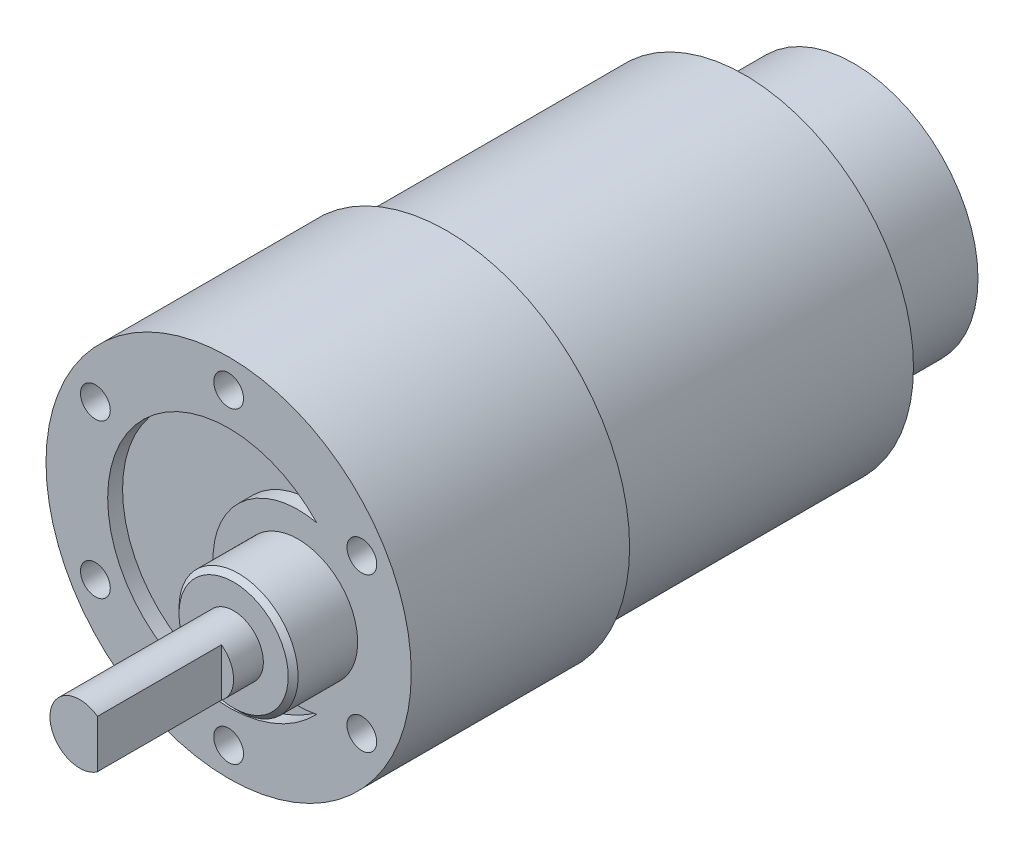
SolidWorks part; units mm, degrees
ref_plane "Front Plane" through (0, 0, 0) normal (0, 0, 1) x (1, 0, 0)
ref_plane "Top Plane" through (0, 0, 0) normal (0, 1, 0) x (1, 0, 0)
ref_plane "Right Plane" through (0, 0, 0) normal (1, 0, 0) x (0, 0, -1)
sketch "Sketch1" plane through (0, 0, 0) normal (0, 0, 1) x (1, 0, 0)
  circle A0 centre (0, 0) radius 17
  dimension "D1" = 34
extrude "Boss-Extrude1" add sketch "Sketch1" along normal blind 30
fillet "Fillet1" radius 1 1 edges at (17, 0, 30)
sketch "Sketch2" plane through (0, 0, 30) normal (0, 0, 1) x (1, 0, 0)
  circle A0 centre (0, 0) radius 18.4
extrude "Boss-Extrude2" add sketch "Sketch2" along normal blind 22
sketch "Sketch3" plane through (0, 0, 52) normal (0, 0, 1) x (1, 0, 0)
  circle A0 centre (0, 15.5) radius 1.5
  circle A1 centre (0, 0) radius 18.4 construction
  circle A2 centre (13.4234, 7.75) radius 1.5
  circle A3 centre (13.4234, -7.75) radius 1.5
  circle A4 centre (0, -15.5) radius 1.5
  circle A5 centre (-13.4234, -7.75) radius 1.5
  circle A6 centre (-13.4234, 7.75) radius 1.5
  dimension "D1" = 15.5
  dimension "D2" = 6
extrude "Cut-Extrude1" cut sketch "Sketch3" against normal blind 3
sketch "Sketch4" plane through (0, 0, 52) normal (0, 0, 1) x (1, 0, 0)
  circle A0 centre (7, 0) radius 6
  circle A1 centre (0, 15.5) radius 1.5 construction
  dimension "D1" = 12
  dimension "D2" = 7
extrude "Boss-Extrude3" add sketch "Sketch4" along normal blind 6.5
chamfer "Chamfer1" distance 0.5 angle 45 1 edges at (13, 0, 58.5)
sketch "Sketch5" plane through (0, 0, 58.5) normal (0, 0, 1) x (1, 0, 0)
  circle A0 centre (7, 0) radius 3
extrude "Boss-Extrude4" add sketch "Sketch5" along normal blind 15.5
sketch "Sketch6" plane through (0, 0, 52) normal (0, 0, 1) x (1, 0, 0)
  circle A0 centre (7, 0) radius 8.5659
  circle A1 centre (0, 0) radius 12.1872
extrude "Cut-Extrude3" cut sketch "Sketch6" against normal blind 1.5 contours A0 A1 region at (-3.6559, 0, 52)
sketch "Sketch7" plane through (0, 0, 0) normal (0, 0, -1) x (-1, 0, 0)
  circle A0 centre (0, 0) radius 12.5
  dimension "D1" = 25
extrude "Boss-Extrude5" add sketch "Sketch7" along normal blind 11
sketch "Sketch8" plane through (0, 0, 74) normal (0, 0, 1) x (1, 0, 0)
  line L0 (8.7794, 2.4153) -> (8.7794, -2.4153)
  circle A0 centre (7, 0) radius 3 construction
  arc A1 (8.7794, 2.4153) -> (8.7794, -2.4153) centre (7, 0) cw
extrude "Cut-Extrude4" cut sketch "Sketch8" against normal offset from surface (12.5 mm away) 3 up to face at (12.5, 0, 58.5)
